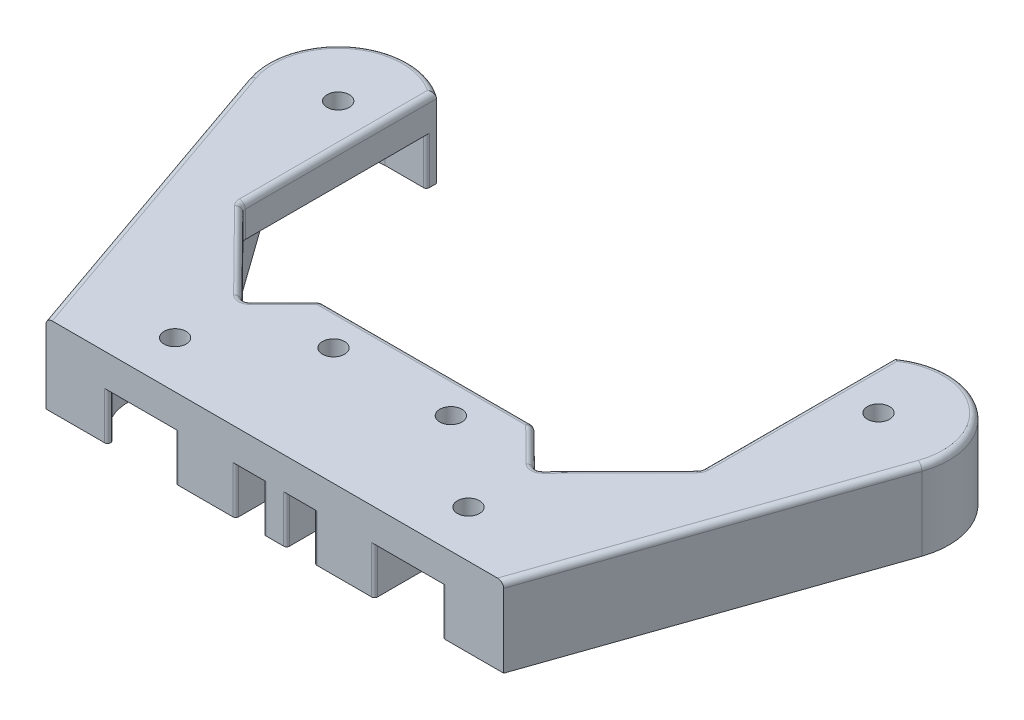
SolidWorks part; units mm, degrees
ref_plane "Front Plane" through (0, 0, 0) normal (0, 0, 1) x (1, 0, 0)
ref_plane "Top Plane" through (0, 0, 0) normal (0, 1, 0) x (1, 0, 0)
ref_plane "Right Plane" through (0, 0, 0) normal (1, 0, 0) x (0, 0, -1)
sketch "Sketch2" plane through (0, 0, 0) normal (0, 1, 0) x (1, 0, 0)
  line L0 (-19.8438, 0) -> (19.8438, 0) construction
  line L1 (0, 0) -> (0, 9.525) construction
  line L2 (0, 9.525) -> (7.9375, 9.525) construction
  line L3 (0, 9.525) -> (-7.9375, 9.525) construction
  line L4 (0, 9.525) -> (0, 38.7629) construction
  line L5 (0, 38.7629) -> (-36.5442, 38.7629) construction
  line L6 (0, 38.7629) -> (36.5442, 38.7629) construction
  line L7 (14.4174, 14.2875) -> (19.7894, 8.9801)
  line L8 (-19.7894, 8.9801) -> (-14.4174, 14.2875)
  line L9 (-30.9563, 46.4766) -> (-30.9562, 20.2828)
  line L10 (-30.9562, 20.2828) -> (-19.7894, 8.9801)
  line L11 (-19.8438, -6.35) -> (19.8438, -6.35)
  line L15 (30.9563, 46.4766) -> (30.9562, 20.2828)
  line L16 (30.9562, 20.2828) -> (19.7894, 8.9801)
  line L17 (-19.8438, -6.35) -> (-30.9562, -6.35)
  line L18 (-30.9562, -6.35) -> (-45.5418, 35.6374)
  line L19 (19.8438, -6.35) -> (30.9562, -6.35)
  line L20 (30.9562, -6.35) -> (45.5418, 35.6374)
  line L21 (-14.4174, 14.2875) -> (14.4174, 14.2875)
  circle A0 centre (-19.8438, 0) radius 1.5
  circle A1 centre (19.8438, 0) radius 1.5
  circle A2 centre (-7.9375, 9.525) radius 1.5
  circle A3 centre (7.9375, 9.525) radius 1.5
  circle A4 centre (-19.8438, 0) radius 6 construction
  circle A5 centre (-7.9375, 9.525) radius 6 construction
  circle A6 centre (7.9375, 9.525) radius 6 construction
  circle A7 centre (19.8438, 0) radius 6 construction
  circle A8 centre (-36.5442, 38.7629) radius 1.5
  circle A9 centre (36.5442, 38.7629) radius 1.5
  circle A10 centre (-36.5442, 38.7629) radius 6 construction
  circle A11 centre (36.5442, 38.7629) radius 6 construction
  arc A12 (-30.9563, 46.4766) -> (-45.5418, 35.6374) centre (-36.5442, 38.7629) ccw
  arc A13 (45.5418, 35.6374) -> (30.9563, 46.4766) centre (36.5442, 38.7629) ccw
  circle A14 centre (-36.5442, 38.7629) radius 6.35 construction
  circle A15 centre (36.5442, 38.7629) radius 6.35 construction
  circle A20 centre (-19.8438, 0) radius 6.35 construction
  circle A21 centre (-7.9375, 9.525) radius 6.35 construction
  circle A22 centre (7.9375, 9.525) radius 6.35 construction
  circle A23 centre (19.8438, 0) radius 6.35 construction
  point P3 (0, -6.35)
  point P4 (0, 0)
  point P24 (0, 14.2875)
  point P29 (0, 0)
  dimension "D2" = 3
  dimension "D5" = 12
  dimension "D8" = 19.05
  dimension "D9" = 12.7
  dimension "D12" = 6.35
  dimension "D1" = 9.525
  dimension "D3" = 39.6875
  dimension "D4" = 7.9375
  dimension "D6" = 29.2379
  dimension "D7" = 36.5442
  dimension "D10" = 5.588
  dimension "D11" = 26.1937
  dimension "D14" = 61.9125
  dimension "D15" = 20.6375
extrude "Boss-Extrude1" add sketch "Sketch2" along normal blind 10.7315
sketch "Sketch3" plane through (0, 0, 0) normal (0, -1, 0) x (1, 0, 0)
  line L1 (-1.5875, -9.525) -> (-1.5875, 6.35)
  line L6 (-36.5442, -45.1129) -> (-30.9563, -45.1129)
  line L7 (-30.9563, -46.4766) -> (-30.9562, -20.2828) construction
  line L8 (-41.7061, -35.0647) -> (-21.0504, -6.2343)
  line L9 (-30.9562, -26.4134) -> (-14.6819, -3.6983)
  line L10 (-16.1857, -2.6208) -> (-40.2023, -36.1421) construction
  line L11 (-30.9563, -45.1129) -> (-30.9562, -26.4134)
  line L13 (-13.4937, 0) -> (-13.4938, 6.35)
  line L14 (-19.8438, 6.35) -> (19.8438, 6.35) construction
  line L18 (-21.0504, -6.2343) -> (-18.0427, -8.3892) construction
  line L21 (-17.1938, 6.35) -> (-13.4938, 6.35)
  line L25 (-5.2875, -3.7544) -> (-5.2875, 6.35)
  line L27 (-5.2875, 6.35) -> (-1.5875, 6.35)
  line L29 (-3.4474, -14.0151) -> (-3.7197, -14.2875)
  line L34 (0, 0) -> (0, -14.2875) construction
  line L36 (-3.7197, -14.2875) -> (-12.1376, -14.2875)
  line L37 (21.0504, -6.2343) -> (18.0427, -8.3892) construction
  line L38 (16.1857, -2.6208) -> (40.2023, -36.1421) construction
  line L40 (3.4474, -14.0151) -> (3.7197, -14.2875)
  line L41 (5.2875, 6.35) -> (1.5875, 6.35)
  line L42 (5.2875, -3.7544) -> (5.2875, 6.35)
  line L43 (17.1938, 6.35) -> (13.4938, 6.35)
  line L45 (13.4937, 0) -> (13.4938, 6.35)
  line L46 (30.9562, -45.1129) -> (30.9562, -26.4134)
  line L47 (30.9562, -26.4134) -> (14.6819, -3.6983)
  line L48 (41.7061, -35.0647) -> (21.0504, -6.2343)
  line L49 (36.5442, -45.1129) -> (30.9562, -45.1129)
  line L50 (1.5875, -9.525) -> (1.5875, 6.35)
  line L51 (-19.8438, 6.35) -> (-17.1938, 6.35)
  line L52 (19.8438, 6.35) -> (17.1938, 6.35)
  line L57 (3.7197, -14.2875) -> (12.1376, -14.2875)
  line L58 (14.4174, -14.2875) -> (-14.4174, -14.2875) construction
  arc A0 (-19.8438, 6.35) -> (-21.0504, -6.2343) centre (-19.8438, 0) ccw
  circle A2 centre (-7.9375, -9.525) radius 6.35 construction
  arc A4 (-5.2875, -3.7544) -> (-12.1376, -14.2875) centre (-7.9375, -9.525) ccw
  circle A5 centre (-7.9375, -9.525) radius 4.5 construction
  circle A12 centre (-36.5442, -38.7629) radius 6.35 construction
  arc A13 (-41.7061, -35.0647) -> (-36.5442, -45.1129) centre (-36.5442, -38.7629) ccw
  circle A16 centre (19.8438, 0) radius 4.5 construction
  circle A17 centre (-19.8438, 0) radius 6.35 construction
  arc A30 (-14.6819, -3.6983) -> (-13.4937, 0) centre (-19.8438, 0) ccw
  circle A31 centre (-36.5442, -38.7629) radius 4.5 construction
  circle A32 centre (-19.8438, 0) radius 4.5 construction
  arc A33 (-3.4474, -14.0151) -> (-1.5875, -9.525) centre (-7.9375, -9.525) ccw
  circle A34 centre (36.5442, -38.7629) radius 4.5 construction
  circle A35 centre (7.9375, -9.525) radius 4.5 construction
  arc A36 (3.4474, -14.0151) -> (1.5875, -9.525) centre (7.9375, -9.525) cw
  arc A37 (14.6819, -3.6983) -> (13.4937, 0) centre (19.8438, 0) cw
  arc A38 (41.7061, -35.0647) -> (36.5442, -45.1129) centre (36.5442, -38.7629) cw
  arc A39 (5.2875, -3.7544) -> (12.1376, -14.2875) centre (7.9375, -9.525) cw
  arc A41 (19.8438, 6.35) -> (21.0504, -6.2343) centre (19.8438, 0) cw
  point P28 (0, 0)
  point P31 (0, 0)
  point P32 (0, -14.2875)
  dimension "D1" = 9
  dimension "D2" = 45
extrude "Cut-Extrude1" cut sketch "Sketch3" against normal blind 6.3805 and the other way through all
fillet "Fillet1" radius 0.3969 20 edges at (30.9562, 3.1902, -45.1129) (13.4938, 3.1902, 6.35) (19.0145, 3.1902, -9.7457) (5.2875, 3.1902, 6.35) (1.5875, 3.1902, 6.35) (-1.5875, 3.1902, 6.35) (-5.2875, 3.1902, 6.35) (-30.9563, 3.1902, -45.1129) (-19.0145, 3.1902, -9.7457) (-13.4938, 3.1902, 6.35) (-3.7197, 3.1902, -14.2875) (3.7197, 3.1902, -14.2875)
sketch "Sketch4" plane through (0, 6.3805, 0) normal (0, -1, 0) x (1, 0, 0)
  circle A0 centre (-19.8438, 0) radius 3
  circle A1 centre (-36.5442, -38.7629) radius 3
  circle A2 centre (-7.9375, -9.525) radius 3
  circle A3 centre (7.9375, -9.525) radius 3
  circle A4 centre (19.8438, 0) radius 3
  circle A5 centre (36.5442, -38.7629) radius 3
  circle A6 centre (36.5442, -38.7629) radius 1.5 construction
  circle A7 centre (19.8438, 0) radius 1.5 construction
  circle A8 centre (7.9375, -9.525) radius 1.5 construction
  circle A9 centre (-7.9375, -9.525) radius 1.5 construction
  circle A10 centre (-36.5442, -38.7629) radius 1.5 construction
  circle A11 centre (-19.8438, 0) radius 1.5 construction
  circle A12 centre (36.5442, -38.7629) radius 1.5
  circle A13 centre (19.8438, 0) radius 1.5
  circle A14 centre (7.9375, -9.525) radius 1.5
  circle A15 centre (-7.9375, -9.525) radius 1.5
  circle A16 centre (-36.5442, -38.7629) radius 1.5
  circle A17 centre (-19.8438, 0) radius 1.5
  dimension "D1" = 6
extrude "Boss-Extrude3" add sketch "Sketch4" along normal blind 0.7937
chamfer "Chamfer1" distance 0.7937 angle 45 6 edges at (36.5442, 6.3805, -35.7629) (19.8438, 6.3805, 3) (7.9375, 6.3805, -6.525) (-7.9375, 6.3805, -12.525) (-36.5442, 6.3805, -41.7629) (-19.8438, 6.3805, -3)
fillet "Fillet2" radius 0.7937 6 edges at (-14.4174, 5.3658, -14.2875) (14.4174, 5.3658, -14.2875)
fillet "Fillet3" radius 0.7937 17 edges at (-38.249, 10.7315, -14.6437) (30.9563, 10.7315, -33.5427) (30.8967, 10.7315, -20.3072) (-30.9563, 10.7315, -33.5427) (-30.8967, 10.7315, -20.3072) (-25.5372, 10.7315, -14.7978) (-19.7874, 10.7315, -9.3089) (-16.9371, 10.7315, -11.7982) (16.9371, 10.7315, -11.7982) (19.7874, 10.7315, -9.3089) (42.2257, 10.7315, -46.408) (-42.2257, 10.7315, -46.408) (25.5372, 10.7315, -14.7978) (38.249, 10.7315, -14.6437) (-14.393, 10.7315, -14.228) (0, 10.7315, -14.2875) (14.393, 10.7315, -14.228)
